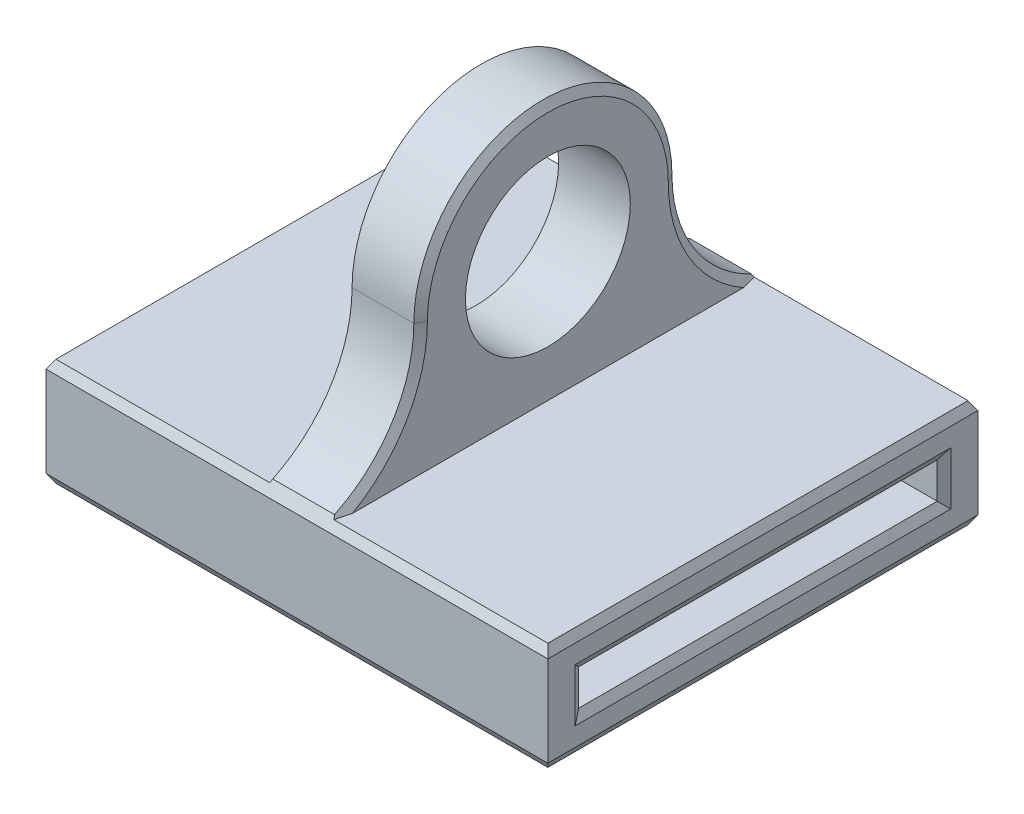
SolidWorks part; units mm, degrees
ref_plane "정면" through (0, 0, 0) normal (0, 0, 1) x (1, 0, 0)
ref_plane "윗면" through (0, 0, 0) normal (0, 1, 0) x (1, 0, 0)
ref_plane "우측면" through (0, 0, 0) normal (1, 0, 0) x (0, 0, -1)
sketch "스케치1" plane through (0, 0, 0) normal (0, 1, 0) x (1, 0, 0)
  line L1 (-35, -30) -> (35, -30)
  line L2 (-35, -30) -> (-35, 30)
  line L3 (-35, 30) -> (35, 30)
  line L4 (35, -30) -> (35, 30)
  line L5 (-35, -30) -> (35, 30) construction
  line L6 (-35, 30) -> (35, -30) construction
  point P0 (0, 0)
  dimension "D1" = 60
  dimension "D2" = 70
extrude "보스-돌출1" add sketch "스케치1" along normal blind 15
sketch "스케치2" plane through (0, 0, 0) normal (1, 0, 0) x (0, 0, -1)
  line L0 (0, 15) -> (0, 33) construction
  line L2 (30, 15) -> (-30, 15) construction
  line L3 (30, 15) -> (-30, 15)
  circle A0 centre (0, 33) radius 11.5
  circle A1 centre (0, 33) radius 18
  arc A2 (18, 33) -> (30, 15) centre (37.5, 33) ccw
  arc A3 (-18, 33) -> (-30, 15) centre (-37.5, 33) cw
  dimension "D1" = 36
  dimension "D2" = 6.5
extrude "보스-돌출3" add sketch "스케치2" along normal mid plane 10
sketch "스케치3" plane through (0, 0, 0) normal (1, 0, 0) x (0, 0, -1)
  line L0 (0, 15) -> (0, 0) construction
  line L1 (30, 15) -> (-30, 15) construction
  line L3 (25, 5) -> (-25, 5)
  line L4 (25, 5) -> (25, 10)
  line L5 (25, 10) -> (-25, 10)
  line L6 (-25, 5) -> (-25, 10)
  line L7 (25, 5) -> (-25, 10) construction
  line L8 (25, 10) -> (-25, 5) construction
  point P5 (0, 7.5)
  dimension "D1" = 5
  dimension "D2" = 50
extrude "컷-돌출1" cut sketch "스케치3" against normal through all both and the other way through all
chamfer "모따기1" distance 1.2 angle 30 4 edges at (35, 0, 0) (0, 0, 30) (-35, 0, 0) (0, 0, -30)
chamfer "모따기2" distance 1.2 angle 30 4 edges at (35, 15, 0) (-35, 15, 0) (0, 15, -30) (0, 15, 30)
chamfer "모따기3" distance 1.2 angle 30 6 edges at (5, 22.613, -20.9966) (5, 22.613, 20.9966) (5, 51, 0) (-5, 22.613, -20.9966) (-5, 51, 0) (-5, 22.613, 20.9966)
chamfer "모따기4" distance 1.2 angle 30 8 edges at (35, 7.5, -25) (35, 10, 0) (35, 7.5, 25) (35, 5, 0) (-35, 7.5, -25) (-35, 10, 0) (-35, 7.5, 25) (-35, 5, 0)
